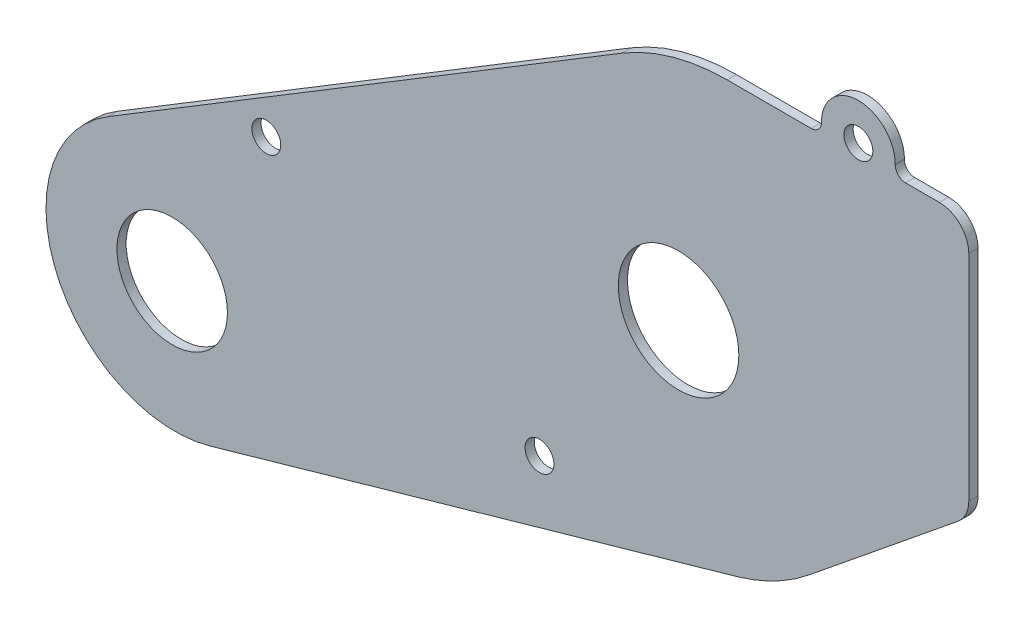
SolidWorks part; units mm, degrees
material "ABS PC"
ref_plane "Front Plane" through (0, 0, 0) normal (0, 0, 1) x (1, 0, 0)
ref_plane "Top Plane" through (0, 0, 0) normal (0, 1, 0) x (1, 0, 0)
ref_plane "Right Plane" through (0, 0, 0) normal (1, 0, 0) x (0, 0, -1)
sketch "Sketch2" plane through (0, 0, 0) normal (0, 0, 1) x (1, 0, 0)
  line L0 (25.0911, -52.0924) -> (-65.6838, -78.0001)
  line L1 (-83.3142, -37.6288) -> (5.2713, 16.1338)
  line L2 (52.3571, 23.0853) -> (52.3571, 22.9801)
  line L3 (-59.5064, -69.3804) -> (-85.0103, -43.8765) construction
  line L5 (63.1592, -24.8058) -> (37.5195, -45.6224)
  line L7 (39.6571, 23.0853) -> (39.6571, 22.9801)
  line L8 (54.1351, 21.2021) -> (59.9573, 21.2021)
  line L10 (65.831, 16.0128) -> (55.9968, 5.3253) construction
  line L11 (42.2751, -9.5867) -> (65.831, 16.0128) construction
  line L12 (65.831, 16.0128) -> (65.831, 22.3102) construction
  line L14 (37.8791, 21.2021) -> (23.3913, 21.2021)
  line L15 (65.0373, 16.1221) -> (65.0373, -20.8619)
  arc A3 (37.5195, -45.6224) -> (25.0911, -52.0924) centre (15.506, -18.5085) cw
  arc A4 (-83.3142, -37.6288) -> (-65.6838, -78.0001) centre (-71.7833, -56.6285) ccw
  circle A8 centre (15.0168, -18.8831) radius 10.3877
  circle A9 centre (-72.2583, -56.6285) radius 9.525
  arc A12 (59.9573, 21.2021) -> (65.0373, 16.1221) centre (59.9573, 16.1221) cw
  arc A13 (63.1592, -24.8058) -> (65.0373, -20.8619) centre (59.9573, -20.8619) ccw
  arc A14 (5.2713, 16.1338) -> (23.3913, 21.2021) centre (23.3913, -13.7229) cw
  arc A16 (52.3571, 23.0853) -> (39.6571, 23.0853) centre (46.0071, 23.0853) ccw
  arc A17 (52.3571, 22.9801) -> (54.1351, 21.2021) centre (54.1351, 22.9801) ccw
  arc A18 (39.6571, 22.9801) -> (37.8791, 21.2021) centre (37.8791, 22.9801) cw
  point P19 (-72.2583, -56.6285)
  point P20 (15.506, -18.5085)
  point P36 (52.3571, 21.2021)
  dimension "D1" = 5.08
  dimension "D2" = 5.08
  dimension "D4" = 1.778
  dimension "D3" = 34.925
extrude "Boss-Extrude1" add sketch "Sketch2" along normal blind 1.5875
sketch "Sketch4" plane through (0, 0, 1.5875) normal (0, 0, 1) x (1, 0, 0)
  line L0 (-58.677, -22.6764) -> (-56.0414, -27.0192) construction
  line L1 (5.2713, 16.1338) -> (-83.3142, -37.6288) construction
  line L2 (-6.9135, -55.744) -> (-8.9513, -51.0906) construction
  line L3 (-62.0382, -79.8833) -> (25.1671, -41.6958) construction
  circle A1 centre (-56.0414, -27.0192) radius 3.9687 construction
  circle A2 centre (-8.9513, -51.0906) radius 3.9688 construction
  point P15 (46.0071, 23.0853)
hole_wizard "#10 Clearance Hole1" positions "Sketch5" profile "Sketch6" hole size "#10" standard "ANSI Inch" end condition through all
sketch "Sketch5" plane through (0, 0, 1.5875) normal (0, 0, 1) x (1, 0, 0)
  point P0 (-56.0414, -27.0192)
  point P3 (-8.9513, -51.0906)
  point P6 (46.0071, 23.0853)
sketch "Sketch6" plane through (-56.0414, -27.0192, 1.5875) normal (1, 0, 0) x (0, -1, 0)
  line L0 (0, 0) -> (0, 1.5875)
  line L1 (0, 1.5875) -> (2.4892, 1.5875)
  line L2 (2.4892, 1.5875) -> (2.4892, 0)
  line L5 (2.4892, 0) -> (0, 0)
  line L11 (0, -6.35) -> (0, 107.95) construction
  dimension "Thru Hole Dia." = 4.9784
  dimension "Thru Hole Depth" = 1.5875
